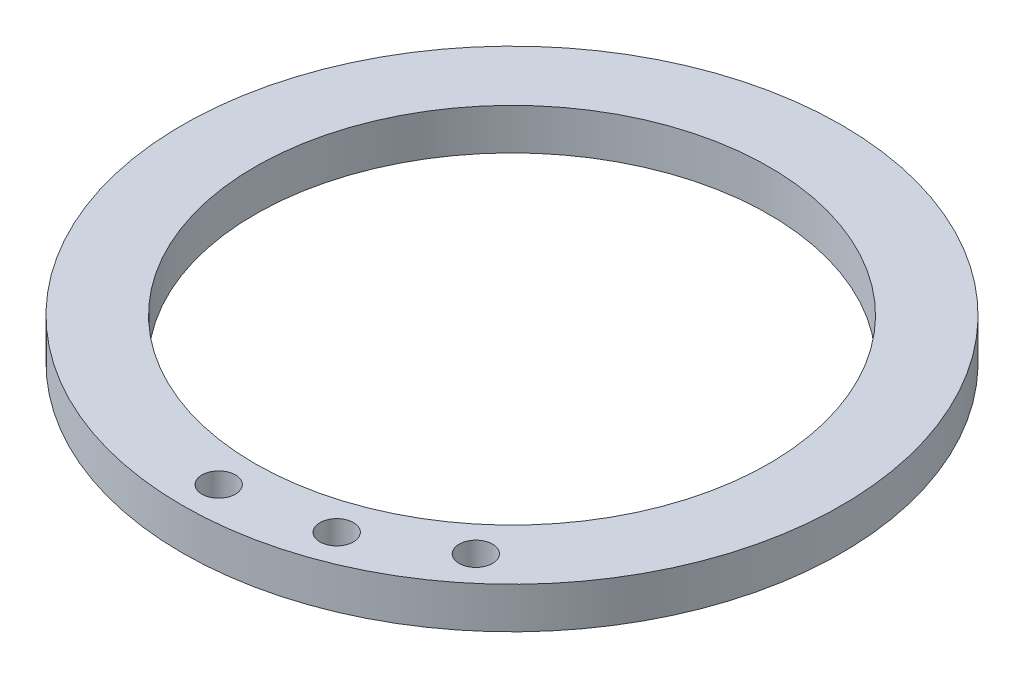
SolidWorks part; units mm, degrees
material "C-Glass Fiber"
ref_plane "Front Plane" through (0, 0, 0) normal (0, 0, 1) x (1, 0, 0)
ref_plane "Top Plane" through (0, 0, 0) normal (0, 1, 0) x (1, 0, 0)
ref_plane "Right Plane" through (0, 0, 0) normal (1, 0, 0) x (0, 0, -1)
sketch "Sketch1" plane through (0, 0, 0) normal (0, 1, 0) x (1, 0, 0)
  circle A0 centre (0, 0) radius 39.624
  circle A1 centre (0, 0) radius 50.8
  dimension "D1" = 101.6
  dimension "D2" = 79.248
extrude "Ring Extrusion" add sketch "Sketch1" along normal blind 6.35 contours A1 | A0
sketch "Sketch2" plane through (0, 0, 0) normal (0, 1, 0) x (1, 0, 0)
  circle A0 centre (0, -45.212) radius 2.5797
  circle A2 centre (0, 0) radius 45.212 construction
  circle A5 centre (0, 0) radius 50.8 construction
  circle A6 centre (0, 0) radius 39.624 construction
  circle A7 centre (0, 0) radius 50.8 construction
  circle A8 centre (0, 0) radius 39.624 construction
  dimension "D1" = 5.1594
  dimension "D2" = 79.248
  dimension "D3" = 101.6
  dimension "D4" = 90.424
extrude "Conduit Hole" cut sketch "Sketch2" along normal through all
pattern_circular "CirPattern1" count 3 every 20 about axis through (0, 6.35, 0) along (0, 1, 0) of "Conduit Hole"
equation "\"D4@Sketch2\"=(\"D2@Sketch2\"+\"D3@Sketch2\")/2"
